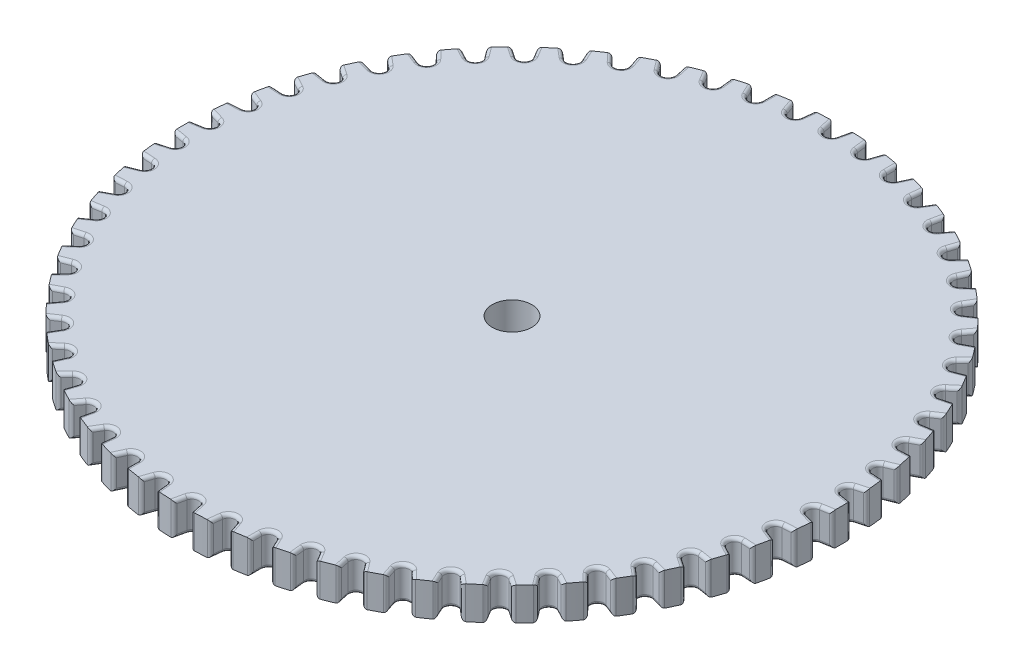
SolidWorks part; units mm, degrees
ref_plane "Front Plane" through (0, 0, 0) normal (0, 0, 1) x (1, 0, 0)
ref_plane "Top Plane" through (0, 0, 0) normal (0, 1, 0) x (1, 0, 0)
ref_plane "Right Plane" through (0, 0, 0) normal (1, 0, 0) x (0, 0, -1)
sketch "Sketch2" plane through (0, 0, 0) normal (0, 1, 0) x (1, 0, 0)
  circle A0 centre (0, 0) radius 100
  dimension "D1" = 200
extrude "Boss-Extrude2" add sketch "Sketch2" along normal mid plane 10
sketch "Sketch3" plane through (0, 5, 0) normal (0, 1, 0) x (1, 0, 0)
  line L1 (1.9525, 96.6639) -> (2.685, 99.9639)
  line L2 (0, 97.0973) -> (0, 0) construction
  line L4 (-1.9525, 96.6639) -> (-2.685, 99.9639)
  arc A0 (2.685, 99.9639) -> (-2.685, 99.9639) centre (0, 0) ccw
  arc A1 (-1.9525, 96.6639) -> (1.9525, 96.6639) centre (0, 97.0973) ccw
  circle A6 centre (0, 0) radius 100 construction
  point P0 (0, 17.9807)
  dimension "D2" = 4
  dimension "D3" = 25.03
  dimension "D1" = 3.3
sketch "Sketch4" plane through (0, 5, 0) normal (0, 1, 0) x (1, 0, 0)
  circle A0 centre (0, 0) radius 6
  dimension "D1" = 12
extrude "Cut-Extrude3" cut sketch "Sketch4" against normal blind 10
extrude "Cut-Extrude5" cut sketch "Sketch3" against normal blind 10
fillet "Fillet1" radius 1 8 edges at (2.3187, -5, -98.3139) (2.3187, 5, -98.3139) (0, -5, -95.0973) (0, 5, -95.0973) (-2.685, 0, -99.9639) (-2.3187, -5, -98.3139) (-2.3187, 5, -98.3139) (2.685, 0, -99.9639)
pattern_circular "CirPattern3" count 58 over 360 about axis through (0, 5, 0) along (0, 1, 0) of face at (-2.229, 0, -97.9097) of face at (0, 0, -95.8806) of face at (2.229, 0, -97.9097) of face at (2.8339, 4.666, -98.4735) of face at (0, 4.6036, -95.5989) of face at (-2.8709, 4.6693, -98.4721) of face at (-2.9405, 0, -99.6382) of face at (-2.8339, -4.666, -98.4735) of face at (0, -4.6036, -95.5989) of face at (2.8709, -4.6693, -98.4721) of face at (2.9405, 0, -99.6382)
